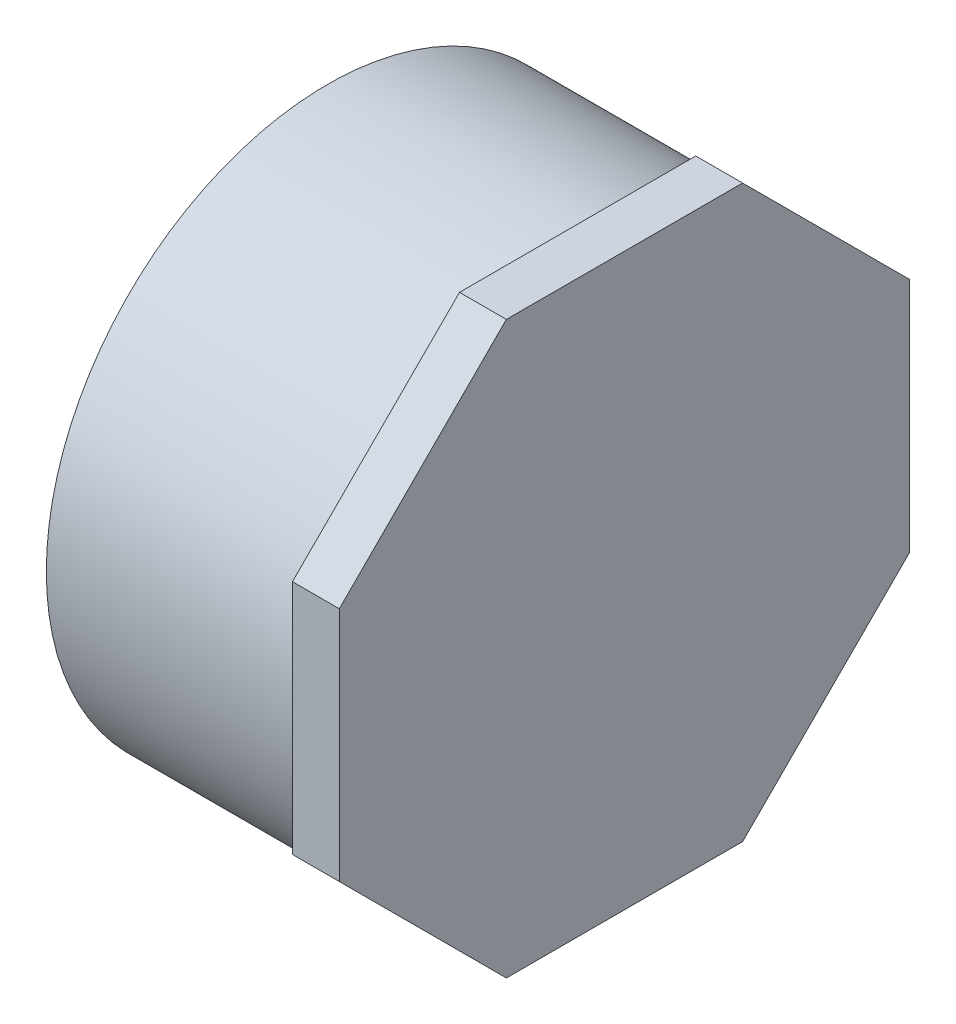
SolidWorks part; units mm, degrees
ref_plane "Front Plane" through (0, 0, 0) normal (0, 0, 1) x (1, 0, 0)
ref_plane "Top Plane" through (0, 0, 0) normal (0, 1, 0) x (1, 0, 0)
ref_plane "Right Plane" through (0, 0, 0) normal (1, 0, 0) x (0, 0, -1)
sketch "Sketch0" plane through (0, 0, 0) normal (0, 0, 1) x (1, 0, 0)
  line L2 (-30.1625, 57.15) -> (-30.1625, -57.15) construction
  line L3 (-30.1625, 0) -> (30.1625, 0) construction
  line L14 (20.6375, 51.1302) -> (20.6375, -51.1302) construction
  point P5 (20.6375, 0)
  dimension "ID" = 102.2604
  dimension "L" = 60.325
  dimension "C" = 50.8
  dimension "Pipe OD" = 114.3
  dimension "R" = 9.525
  dimension "Wall Thickness" = 6.0198
sketch "Sketch1" plane through (0, 0, 0) normal (0, 0, 1) x (1, 0, 0)
  line L0 (-30.1625, -57.15) -> (30.1625, -57.15)
  line L1 (-30.1625, 0) -> (30.1625, 0) construction
  line L3 (30.1625, 0) -> (20.6375, 0)
  line L4 (20.6375, -51.1302) -> (-30.1625, -51.1302)
  line L5 (-30.1625, -51.1302) -> (-30.1625, -57.15)
  line L6 (-30.1625, 57.15) -> (-30.1625, -57.15) construction
  line L7 (30.1625, 0) -> (30.1625, -57.15)
  line L10 (20.6375, 0) -> (20.6375, -51.1302)
revolve "Revolve1" add sketch "Sketch1" angle 360 about L1
sketch "Sketch2" plane through (30.1625, 0, 0) normal (1, 0, 0) x (0, 0, -1)
  line L0 (0, 66.9077) -> (0, 0) construction
  line L1 (0, 66.9077) -> (-57.9437, 33.4538) construction
  line L2 (-57.9437, 33.4538) -> (-57.9437, -33.4538) construction
  line L3 (-57.9437, -33.4538) -> (0, -66.9077) construction
  line L4 (0, -66.9077) -> (57.9437, -33.4538) construction
  line L5 (57.9437, -33.4538) -> (57.9437, 33.4538) construction
  line L6 (57.9437, 33.4538) -> (0, 66.9077) construction
  line L8 (-24.0011, 57.9438) -> (-57.9438, 24.0011)
  line L9 (-57.9438, 24.0011) -> (-57.9437, -24.0011)
  line L10 (-57.9437, -24.0011) -> (-24.0011, -57.9438)
  line L11 (-24.0011, -57.9438) -> (24.0011, -57.9438)
  line L12 (24.0011, -57.9438) -> (57.9438, -24.0011)
  line L13 (57.9438, -24.0011) -> (57.9438, 24.0011)
  line L14 (57.9438, 24.0011) -> (24.0011, 57.9438)
  line L15 (24.0011, 57.9438) -> (-24.0011, 57.9438)
  circle A0 centre (0, 0) radius 57.9437 construction
  circle A1 centre (0, 0) radius 57.15
  circle A2 centre (0, 0) radius 57.15
  circle A3 centre (0, 0) radius 57.9437 construction
  dimension "D2" = 115.8875
  dimension "D1" = 0
extrude "Boss-Extrude1" add sketch "Sketch2" against normal up to vertex (9.525 mm away) up to point (20.6375, 0, 0)
ref_axis "Axis of Rotation" through (20.6375, 0, 0) along (-1, 0, 0)
other "CPoint1" parameters "Diameter"=101.6, "StubLength"=76.2
ref_axis "Axis2" through (10.6375, 0, 0) along (1, 0, 0)
other "RPoint1"
